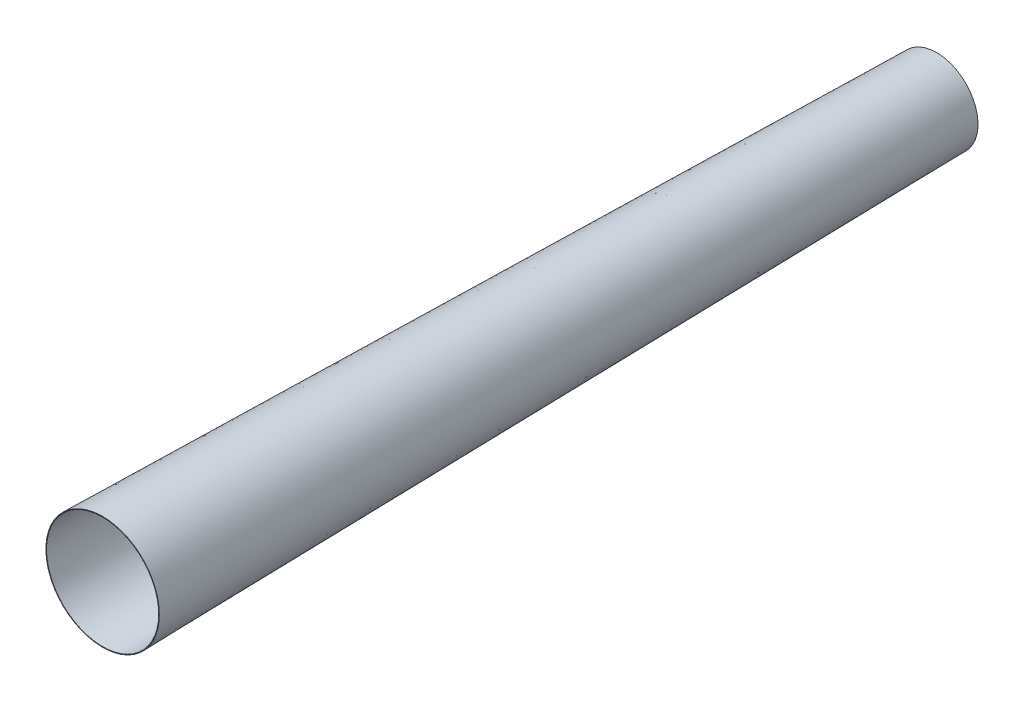
SolidWorks part; units mm, degrees
ref_plane "Front Plane" through (0, 0, 0) normal (0, 0, 1) x (1, 0, 0)
ref_plane "Top Plane" through (0, 0, 0) normal (0, 1, 0) x (1, 0, 0)
ref_plane "Right Plane" through (0, 0, 0) normal (1, 0, 0) x (0, 0, -1)
sketch "Sketch1" plane through (0, 0, 0) normal (0, 0, 1) x (1, 0, 0)
  circle A0 centre (0, 0) radius 34.3114
  circle A1 centre (0, 0) radius 34.8114
  dimension "D2" = 69.6229
  dimension "D1" = 0.5
ref_plane "Plane1" through (0, 0, 700.9946) normal (0, 0, 1) x (1, 0, 0)
sketch "Sketch2" plane through (0, 0, 700.9946) normal (0, 0, 1) x (1, 0, 0)
  circle A0 centre (0, 0) radius 47.6585
  circle A1 centre (0, 0) radius 47.1585
  dimension "D2" = 95.317
  dimension "D1" = 0.5
loft "Loft1" add section "Sketch1" section "Sketch2" start constraint default connector at (-31.489, -14.8418, 0) connector at (-43.1736, -20.1836, 700.9946)
shell "Shell1" thickness 0.5 removed face at (34.8114, 0, 0) removed face at (47.6585, 0, 700.9946)
